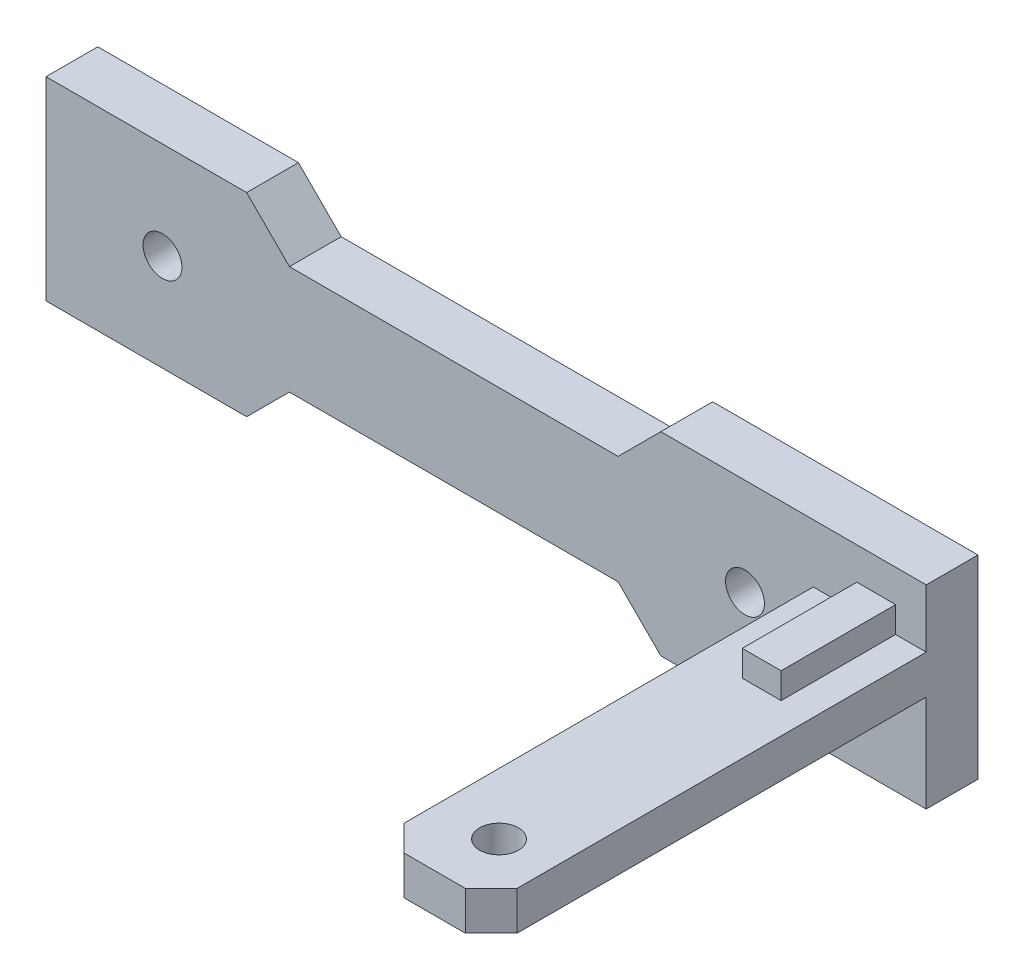
SolidWorks part; units mm, degrees
ref_plane "前视基准面" through (0, 0, 0) normal (0, 0, 1) x (1, 0, 0)
ref_plane "上视基准面" through (0, 0, 0) normal (0, 1, 0) x (1, 0, 0)
ref_plane "右视基准面" through (0, 0, 0) normal (1, 0, 0) x (0, 0, -1)
sketch "草图1" plane through (0, 0, 0) normal (0, 0, 1) x (1, 0, 0)
  line L0 (-22.5, 0) -> (22.5, 0)
  line L1 (0, 0) -> (0, 7.5011)
  line L2 (0, 7.5011) -> (-32, 7.5011)
  line L3 (0, 7.5011) -> (32, 7.5011)
  line L4 (0, -7.5011) -> (-32, -7.5011)
  line L5 (0, -7.5011) -> (32, -7.5011)
  line L6 (-32, 7.5011) -> (-32, -7.5011)
  line L7 (32, -7.5011) -> (32, 7.5011)
  circle A0 centre (22.5, 0) radius 1.5
  circle A1 centre (-22.5, 0) radius 1.5
  point P4 (0, 0)
extrude "凸台-拉伸1" add sketch "草图1" along normal blind 4 contours A1 L2 L6 L4 L5 L7 L3 A0 region at (16, 6.8437, 0)
sketch "草图3" plane through (0, 0, 4) normal (0, 0, 1) x (1, 0, 0)
  line L0 (-22.5, 0) -> (22.5, 0)
  line L1 (22.5, 0) -> (32, 0)
  line L2 (32, -7.5011) -> (32, 7.5011) construction
  line L3 (22.5, 0) -> (31.5, 0)
  line L4 (31.5, 0) -> (31.5, 9.9207)
  line L5 (31.5, 9.9207) -> (32.9805, 9.9207)
  line L6 (32.9805, 9.9207) -> (32.9805, -8.3118)
  line L7 (32.9805, -8.3118) -> (31.5, -8.3118)
  line L8 (31.5, -8.3118) -> (31.5, 0)
  line L9 (0, 0) -> (0, 11.3254)
  line L10 (-31.5, -8.3118) -> (-31.5, 0)
  line L11 (-32.9805, -8.3118) -> (-31.5, -8.3118)
  line L12 (-32.9805, 9.9207) -> (-32.9805, -8.3118)
  line L13 (-31.5, 9.9207) -> (-32.9805, 9.9207)
  line L14 (-31.5, 0) -> (-31.5, 9.9207)
  line M8 (32, -7.5011) -> (32, 7.5011)
  line M9 (32, 7.5011) -> (-32, 7.5011)
  line M10 (-32, 7.5011) -> (-32, -7.5011)
  line M11 (-32, -7.5011) -> (32, -7.5011)
extrude "切除-拉伸2" cut sketch "草图3" against normal blind 4 contours L14 L13 L12 L11 L10 M9 M11 M10 | L10 L14 M9 M10 M11 | L4 L1 M8 M9 | L8 L1 M11 M8 | L8 L7 L6 L5 L4 M9 M8 M11 region at (31.75, 3.7505, 4) region at (31.75, -3.7505, 4) region at (32.4289, 1.114, 4) region at (-32.4289, 1.114, 4) region at (-31.75, 0, 4)
sketch "草图4" plane through (0, 0, 4) normal (0, 0, 1) x (1, 0, 0)
  line L0 (22.5, 0) -> (32.5, 0)
  line L1 (27.5, 0) -> (27.5, 1.8198)
  line L2 (27.5, 1.8198) -> (35.2708, 1.8198)
  line L3 (35.2708, 1.8198) -> (35.2708, -2)
  line L4 (35.2708, -2) -> (27.5, -2)
  line L5 (27.5, -2) -> (27.5, 1.8198)
  circle A0 centre (32.5, 0) radius 2
extrude "凸台-拉伸2" add sketch "草图4" along normal blind 40 contours A0
sketch "草图5" plane through (31.5, 0, 0) normal (1, 0, 0) x (0, 0, -1)
  line L6 (0, 7.5011) -> (-4, 7.5011)
  line L7 (-4, 7.5011) -> (-4, 1.7321)
  line L8 (-4, 1.7321) -> (-4, -1.7321)
  line L9 (-4, -1.7321) -> (-4, -7.5011)
  line L10 (-4, -7.5011) -> (0, -7.5011)
  line L11 (0, -7.5011) -> (0, 7.5011)
  line L12 (0, 7.5011) -> (-4, 7.5011)
  line L13 (-4, 7.5011) -> (-4, 1.7321)
  line L14 (-4, 1.7321) -> (-4, -1.7321)
  line L15 (-4, -1.7321) -> (-4, -7.5011)
  line L16 (-4, -7.5011) -> (0, -7.5011)
  line L17 (0, -7.5011) -> (0, 7.5011)
  dimension "D1" = 0
extrude "凸台-拉伸3" add sketch "草图5" along normal blind 5
sketch "草图7" plane through (0, 0, 44) normal (0, 0, 1) x (1, 0, 0)
  line L0 (30.5, 0) -> (36.5, 0)
  line L1 (36.5, 7.5011) -> (36.5, -7.5011) construction
  line L2 (36.5, 0) -> (36.5, 3)
  line L3 (36.5, 3) -> (30.5, 3)
  line L4 (30.5, 3) -> (30.5, 0)
  line L5 (30.5, 3) -> (27.7741, 3)
  line L6 (27.7741, 3) -> (27.7741, 0)
  line L7 (27.7741, 0) -> (30.8372, 0)
  circle A0 centre (32.5, 0) radius 2 construction
  circle A1 centre (32.5, 0) radius 2 construction
  circle M5 centre (32.5, 0) radius 2
extrude "凸台-拉伸4" add sketch "草图7" against normal up to surface (40 mm away) contours L3 L4 L0 L2 M5 | L6 L7 L4 L5 | L0 M5 region at (32.5, 0.8488, 44) region at (29.1371, 1.5, 44) region at (34.0363, 1.8492, 44) up to face at (34.5, 0, 4)
sketch "草图9" plane through (0, 3, 0) normal (0, 1, 0) x (1, 0, 0)
  line L0 (34.5, -42.1198) -> (30.5, -42.1198)
  line L1 (34.5, -4) -> (34.5, -44) construction
  line L2 (30.5, -44) -> (30.5, -4) construction
  line L3 (32.5, -42.1198) -> (32.5, -25.0076)
  line L4 (32.5, 0) -> (32.5, -32)
  line L5 (36.5, 0) -> (-31.5, 0) construction
  circle A0 centre (32.5, -32) radius 1.5
extrude "切除-拉伸3" cut sketch "草图9" against normal through all both and the other way through all contours L3 A0 | L3 A0 region at (31.8634, 3, 32) region at (33.1366, 3, 32)
sketch "草图10" plane through (0, 0, 44) normal (0, 0, 1) x (1, 0, 0)
  line L0 (27.7741, 0) -> (36.5, 0)
  line L1 (36.5, 0) -> (36.5, -2.2764)
  line L2 (36.5, 0) -> (36.5, -7.5011) construction
  line L3 (36.5, -2.2764) -> (27.7741, -2.2764)
  line L4 (27.7741, -2.2764) -> (27.7741, 0)
extrude "切除-拉伸4" cut sketch "草图10" against normal up to surface (40 mm away) up to face at (20.3548, 0.4, 4)
sketch "草图11" plane through (0, 3, 0) normal (0, 1, 0) x (1, 0, 0)
  line L0 (36.5, 0) -> (36.5, -33)
  line L1 (36.5, -4) -> (36.5, -44) construction
  line L2 (27.7741, -44) -> (27.7741, -36.6066)
  line L3 (27.7741, -4) -> (27.7741, -44) construction
  line L4 (27.7741, -36.6066) -> (36.5, -36.6066)
  line L5 (36.5, -36.6066) -> (36.5, -44)
  line L6 (36.5, -44) -> (27.7741, -44)
  line M3 (27.7741, -4) -> (27.7741, -44)
  line M4 (27.7741, -44) -> (36.5, -44)
  line M5 (36.5, -44) -> (36.5, -4)
extrude "切除-拉伸5" cut sketch "草图11" against normal through all both and the other way through all contours L4 M3 M4 M5 region at (32.1371, 3, 40.3033)
sketch "草图12" plane through (0, 0, 0) normal (0, 0, -1) x (-1, 0, 0)
  line L4 (-36.5, -7.5011) -> (31.5, -7.5011)
  line L5 (31.5, -7.5011) -> (31.5, 7.5011)
  line L6 (31.5, 7.5011) -> (-36.5, 7.5011)
  line L7 (-36.5, 7.5011) -> (-36.5, -7.5011)
  line L8 (-36.5, -7.5011) -> (31.5, -7.5011)
  line L9 (31.5, -7.5011) -> (31.5, 7.5011)
  line L10 (31.5, 7.5011) -> (-36.5, 7.5011)
  line L11 (-36.5, 7.5011) -> (-36.5, -7.5011)
  circle A0 centre (-22.5, 0) radius 1.5 construction
  circle A1 centre (-22.5, 0) radius 1.5
  circle A2 centre (22.5, 0) radius 1.5 construction
  circle A3 centre (22.5, 0) radius 1.5
  dimension "D1" = 0
extrude "凸台-拉伸5" add sketch "草图12" along normal blind 1
sketch "草图13" plane through (0, 0, 4) normal (0, 0, 1) x (1, 0, 0)
  line L8 (36.5, 0) -> (27.7741, 0)
  line L9 (27.7741, 0) -> (27.7741, 3)
  line L10 (27.7741, 3) -> (36.5, 3)
  line L11 (36.5, 3) -> (36.5, 7.5011)
  line L12 (36.5, 7.5011) -> (-31.5, 7.5011)
  line L13 (-31.5, 7.5011) -> (-31.5, -7.5011)
  line L14 (-31.5, -7.5011) -> (36.5, -7.5011)
  line L15 (36.5, -7.5011) -> (36.5, 0)
  line L16 (36.5, 0) -> (27.7741, 0)
  line L17 (27.7741, 0) -> (27.7741, 3)
  line L18 (27.7741, 3) -> (36.5, 3)
  line L19 (36.5, 3) -> (36.5, 7.5011)
  line L20 (36.5, 7.5011) -> (-31.5, 7.5011)
  line L21 (-31.5, 7.5011) -> (-31.5, -7.5011)
  line L22 (-31.5, -7.5011) -> (36.5, -7.5011)
  line L23 (36.5, -7.5011) -> (36.5, 0)
  dimension "D1" = 0
extrude "切除-拉伸6" cut sketch "草图13" against normal blind 1 contours L16 L17 L18 L19 L20 L21 L22 L23
sketch "草图14" plane through (0, 0, 0) normal (0, -1, 0) x (1, 0, 0)
  line L0 (30.988, 3) -> (33.2861, 3)
  line L1 (32.1371, 3) -> (34.1371, 3)
  line L2 (-31.5, 3) -> (36.5, 3) construction
  line L3 (36.5, 3) -> (27.7741, 3) construction
  line L4 (34.1371, 3) -> (34.1371, 11.8478)
  line L5 (34.1371, 11.8478) -> (31.1371, 11.8478)
  line L6 (31.1371, 11.8478) -> (31.1371, 3)
  line L7 (31.1371, 3) -> (34.1371, 3)
  point P3 (32.1371, 3)
  line M7 (27.7741, 3) -> (36.5, 3)
extrude "凸台-拉伸6" add sketch "草图14" along normal blind 2 and the other way blind 5 contours L5 L6 L0 L4 M7 region at (32.6371, 0, 7.4239)
sketch "草图15" plane through (0, 0, 3) normal (0, 0, 1) x (1, 0, 0)
  line L0 (0, 0) -> (0, 7.5011)
  line L1 (36.5, 7.5011) -> (-31.5, 7.5011) construction
  line L2 (-15.9995, 7.5011) -> (15.9995, 7.5011)
  line L3 (15.9995, 7.5011) -> (12.6954, 4.1969)
  line L4 (12.6954, 4.1969) -> (-12.6954, 4.1969)
  line L5 (-15.9995, 7.5011) -> (-12.6954, 4.1969)
  line L6 (-0.4999, 0) -> (14.6424, 0)
  line L7 (-15.9995, -7.5011) -> (15.9995, -7.5011)
  line L8 (15.9995, -7.5011) -> (12.6954, -4.1969)
  line L9 (12.6954, -4.1969) -> (-12.6954, -4.1969)
  line L10 (-15.9995, -7.5011) -> (-12.6954, -4.1969)
  point P10 (0, 4.1969)
  line M10 (36.5, 7.5011) -> (-31.5, 7.5011)
  line M12 (-31.5, -7.5011) -> (36.5, -7.5011)
extrude "切除-拉伸7" cut sketch "草图15" against normal through all both and the other way through all contours L5 L4 L0 M10 | L4 L3 L0 M10 | L10 L8 L9 M12 region at (-7.2054, 5.9124, 3) region at (7.2054, 5.9124, 3) region at (0, -5.9124, 3)
chamfer "倒角1" distance 2 angle 45 2 edges at (27.7741, 1.5, 36.6066) (36.5, 1.5, 36.6066)
